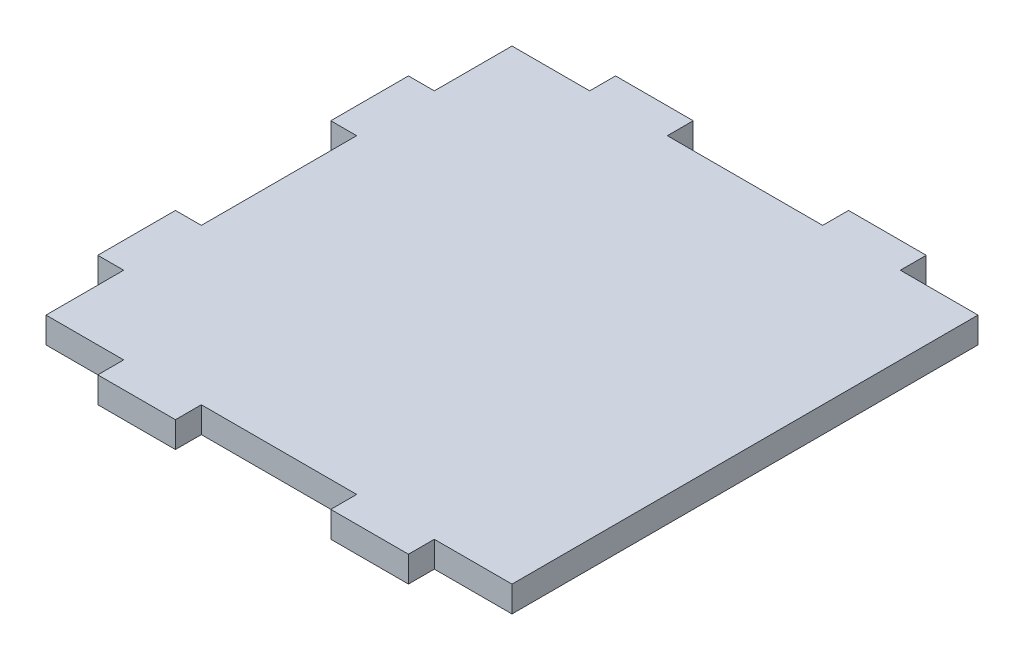
SolidWorks part; units mm, degrees
ref_plane "Front Plane" through (0, 0, 0) normal (0, 0, 1) x (1, 0, 0)
ref_plane "Top Plane" through (0, 0, 0) normal (0, 1, 0) x (1, 0, 0)
ref_plane "Right Plane" through (0, 0, 0) normal (1, 0, 0) x (0, 0, -1)
sketch "Sketch1" plane through (0, 0, 0) normal (0, 1, 0) x (1, 0, 0)
  line L0 (0, 57.15) -> (184.6638, 57.15) construction
  line L1 (0, 0) -> (19.05, 0)
  line L2 (0, 0) -> (0, 19.05)
  line L3 (0, 114.3) -> (19.05, 114.3)
  line L4 (114.3, 0) -> (114.3, 114.3)
  line L5 (38.1, 0) -> (76.2, 0)
  line L7 (95.25, 0) -> (95.25, -6.35)
  line L8 (95.25, -6.35) -> (76.2, -6.35)
  line L9 (76.2, 0) -> (76.2, -6.35)
  line L11 (19.05, 0) -> (19.05, -6.35)
  line L12 (19.05, -6.35) -> (38.1, -6.35)
  line L13 (38.1, 0) -> (38.1, -6.35)
  line L14 (95.25, 0) -> (114.3, 0)
  line L15 (38.1, 114.3) -> (38.1, 120.65)
  line L16 (19.05, 120.65) -> (38.1, 120.65)
  line L17 (19.05, 114.3) -> (19.05, 120.65)
  line L18 (76.2, 114.3) -> (76.2, 120.65)
  line L19 (95.25, 120.65) -> (76.2, 120.65)
  line L20 (95.25, 114.3) -> (95.25, 120.65)
  line L21 (38.1, 114.3) -> (76.2, 114.3)
  line L23 (95.25, 114.3) -> (114.3, 114.3)
  line L24 (-6.35, 19.05) -> (-6.35, 38.1)
  line L25 (0, 95.25) -> (-6.35, 95.25)
  line L27 (0, 76.2) -> (-6.35, 76.2)
  line L28 (-6.35, 95.25) -> (-6.35, 76.2)
  line L29 (0, 38.1) -> (-6.35, 38.1)
  line L31 (0, 19.05) -> (-6.35, 19.05)
  line L32 (0, 95.25) -> (0, 114.3)
  line L33 (0, 38.1) -> (0, 76.2)
  dimension "D1" = 114.3
  dimension "D2" = 114.3
  dimension "D3" = 19.05
  dimension "D4" = 19.05
  dimension "D5" = 19.05
  dimension "D6" = 19.05
  dimension "D7" = 6.35
  dimension "D8" = 6.35
  dimension "D9" = 19.05
  dimension "D10" = 19.05
extrude "Boss-Extrude1" add sketch "Sketch1" against normal blind 6.35
